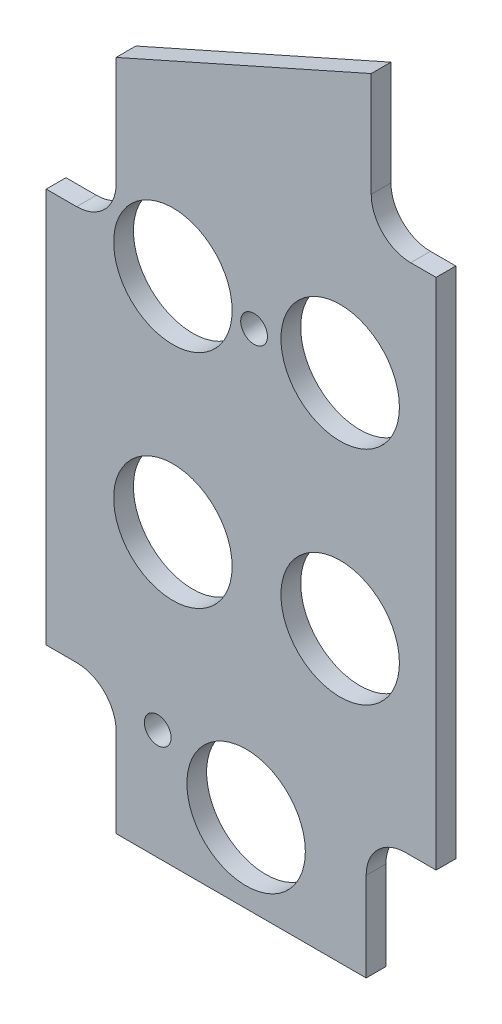
SolidWorks part; units mm, degrees
other "Camera1"
material "PET"
ref_plane "Front Plane" through (0, 0, 0) normal (0, 0, 1) x (1, 0, 0)
ref_plane "Top Plane" through (0, 0, 0) normal (0, 1, 0) x (1, 0, 0)
ref_plane "Right Plane" through (0, 0, 0) normal (1, 0, 0) x (0, 0, -1)
sketch "Sketch1" plane through (0, 0, 0) normal (0, 0, 1) x (1, 0, 0)
  line L8 (0, 103.0909) -> (0, 0)
  line L9 (0, 0) -> (62.6888, 0)
  line L10 (62.6888, 0) -> (62.6888, 131)
  line L11 (62.6888, 131) -> (0, 103.0909)
  dimension "D1" = 131
extrude "Boss-Extrude1" add sketch "Sketch1" against normal blind 3.175
sketch "Sketch2" plane through (0, 0, 0) normal (0, 0, 1) x (1, 0, 0)
  line L0 (0, 0) -> (62.6888, 0) construction
  line L1 (20.3732, 91.7104) -> (20.3732, 82.1854) construction
  line L2 (20.3732, 56.073) -> (20.3732, 46.548) construction
  line L3 (47.2705, 46.548) -> (47.2705, 56.073) construction
  line L4 (32.1439, 22.225) -> (32.1439, 12.7) construction
  line L5 (81.6444, 22.225) -> (81.6444, 12.7) construction
  line L6 (47.2705, 82.1854) -> (47.2705, 91.7104) construction
  line L7 (0, 103.0909) -> (0, 0) construction
  circle A4 centre (32.1439, 12.7) radius 9.525
  circle A10 centre (47.2705, 46.548) radius 9.525
  circle A12 centre (47.2705, 82.1854) radius 9.525
  circle A15 centre (20.3732, 82.1854) radius 9.525
  circle A17 centre (20.3732, 46.548) radius 9.525
  circle A18 centre (81.6444, 22.225) radius 1.651 construction
  circle A19 centre (81.6444, 12.7) radius 9.525 construction
  dimension "D2" = 12.7
  dimension "D3" = 19.05
  dimension "D5" = 19.05
  dimension ".75" = 19.05
  dimension "D1" = 9.525
  dimension "D4" = 32.1439
extrude "Cut-Extrude1" cut sketch "Sketch2" against normal through all
hole_wizard "#6 Clearance Hole1" positions "Sketch4" profile "Sketch3" hole size "#6" standard "ANSI Inch" end condition through all
sketch "Sketch4" plane through (0, 0, 0) normal (0, 0, 1) x (1, 0, 0)
  point P0 (58.6105, 14.2875)
  point P3 (4.8895, 14.2875)
  point P6 (4.8895, 90.4875)
  point P9 (58.6105, 109.5375)
sketch "Sketch3" plane through (58.6105, 14.2875, 0) normal (1, 0, 0) x (0, -1, 0)
  line L0 (0, 0) -> (0, 3.175)
  line L1 (0, 3.175) -> (2.1526, 3.175)
  line L2 (2.1526, 3.175) -> (2.1526, 0)
  line L5 (2.1526, 0) -> (0, 0)
  line L11 (0, -6.35) -> (0, 107.95) construction
  dimension "Thru Hole Dia." = 4.3053
  dimension "Thru Hole Depth" = 3.175
sketch "Sketch5" plane through (0, 0, 0) normal (0, 0, 1) x (1, 0, 0)
  line L0 (0, 0) -> (11.24, 0)
  line L1 (0, 0) -> (62.6888, 0) construction
  line L2 (0, 0) -> (0, 20.64)
  line L3 (0, 103.0909) -> (0, 0) construction
  line L4 (0, 20.64) -> (4.89, 20.64)
  line L5 (11.24, 14.29) -> (11.24, 0)
  line L6 (31.3444, 0) -> (31.3444, 117.0455) construction
  line L7 (62.6888, 131) -> (0, 103.0909) construction
  line L8 (51.4488, 14.29) -> (51.4488, 0)
  line L9 (62.6888, 20.64) -> (57.7988, 20.64)
  line L10 (62.6888, 0) -> (62.6888, 20.64)
  line L11 (62.6888, 0) -> (51.4488, 0)
  line L12 (0, 103.0909) -> (0, 84.1375)
  line L13 (0, 84.1375) -> (4.8895, 84.1375)
  line L14 (11.2395, 90.4875) -> (11.2395, 108.0948)
  line L15 (11.2395, 108.0948) -> (0, 103.0909)
  line L16 (62.6888, 131) -> (62.6888, 103.1875)
  line L17 (62.6888, 0) -> (62.6888, 131) construction
  line L18 (62.6888, 103.1875) -> (58.6105, 103.1875)
  line L19 (52.2605, 109.5375) -> (52.2605, 126.3573)
  line L20 (52.2605, 126.3573) -> (62.6888, 131)
  arc A0 (4.89, 20.64) -> (11.24, 14.29) centre (4.89, 14.29) cw
  arc A1 (57.7988, 20.64) -> (51.4488, 14.29) centre (57.7988, 14.29) ccw
  arc A2 (58.6105, 103.1875) -> (52.2605, 109.5375) centre (58.6105, 109.5375) cw
  arc A3 (4.8895, 84.1375) -> (11.2395, 90.4875) centre (4.8895, 90.4875) ccw
  dimension "D3" = 6.35
  dimension "D6" = 6.35
  dimension "D1" = 11.24
  dimension "D2" = 20.64
extrude "Cut-Extrude2" cut sketch "Sketch5" against normal through all
hole_wizard "#6 Clearance Hole2" positions "Sketch6" profile "Sketch7" hole size "#6" standard "ANSI Inch" end condition through all
sketch "Sketch6" plane through (31.75, 0, 1.59) normal (0, 0, 1) x (1, 0, 0)
  point P0 (1.6763, 81.3834)
  point P2 (-13.8187, 17.7712)
sketch "Sketch7" plane through (33.4263, 81.3834, 1.59) normal (1, 0, 0) x (0, -1, 0)
  line L0 (0, 0) -> (0, 4.765)
  line L1 (0, 4.765) -> (2.1526, 4.765)
  line L2 (2.1526, 4.765) -> (2.1526, 0)
  line L3 (2.1526, 0) -> (0, 0)
  line L4 (0, -6.35) -> (0, 107.95) construction
  dimension "Thru Hole Dia." = 4.3053
  dimension "Thru Hole Depth" = 4.765
